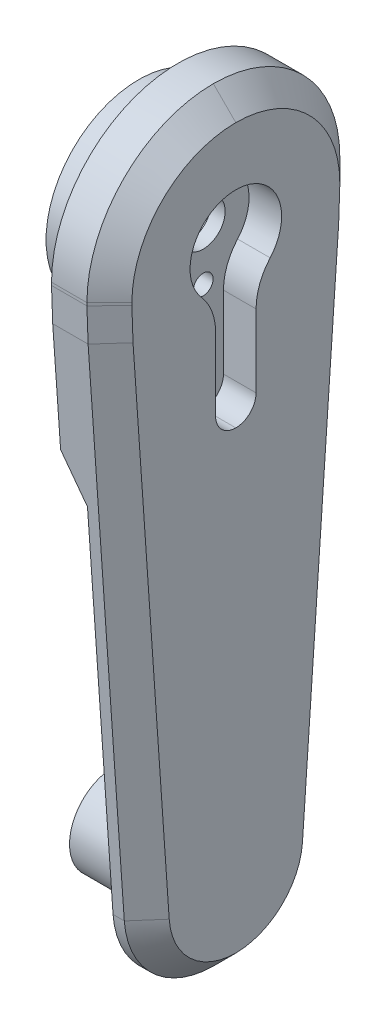
SolidWorks part; units mm, degrees
ref_plane "Front Plane" through (0, 0, 0) normal (0, 0, 1) x (1, 0, 0)
ref_plane "Top Plane" through (0, 0, 0) normal (0, 1, 0) x (1, 0, 0)
ref_plane "Right Plane" through (0, 0, 0) normal (1, 0, 0) x (0, 0, -1)
sketch "Sketch1" plane through (0, 0, 0) normal (1, 0, 0) x (0, 0, -1)
  line L1 (-10, 10) -> (10, 10)
  line L2 (-10, 10) -> (-10, -10)
  line L3 (-10, -10) -> (10, -10)
  line L4 (10, 10) -> (10, -10)
  line L5 (-10, 10) -> (10, -10) construction
  line L6 (-10, -10) -> (10, 10) construction
  point P0 (0, 0)
  dimension "D1" = 20
  dimension "D2" = 20
extrude "Boss-Extrude1" add sketch "Sketch1" along normal blind 20
sketch "Sketch2" plane through (20, 0, 0) normal (1, 0, 0) x (0, 0, -1)
  line L1 (-22.5, 35) -> (22.5, 35)
  line L2 (-22.5, 35) -> (-22.5, -35)
  line L3 (-22.5, -35) -> (22.5, -35)
  line L4 (22.5, 35) -> (22.5, -35)
  line L5 (-22.5, 35) -> (22.5, -35) construction
  line L6 (-22.5, -35) -> (22.5, 35) construction
  point P0 (0, 0)
  dimension "D1" = 45
  dimension "D2" = 70
extrude "Boss-Extrude2" add sketch "Sketch2" along normal blind 8.3
sketch "Sketch4" plane through (28.3, 0, 0) normal (1, 0, 0) x (0, 0, -1)
  line L0 (0, 7.65) -> (0, 8.1702) construction
  line L1 (7.65, 7.65) -> (-7.65, 7.65) construction
  line L17 (3.6, -26.55) -> (-3.6, -26.55) construction
  line L18 (-7.65, 7.65) -> (7.65, 7.65) construction
  line L22 (-7.65, 7.65) -> (-7.65, -27.55) construction
  line L23 (-7.65, -27.55) -> (7.65, -27.55) construction
  line L24 (7.65, 7.65) -> (7.65, -27.55) construction
  line L25 (-7.65, 7.65) -> (7.65, -27.55) construction
  line L26 (-7.65, -27.55) -> (7.65, 7.65) construction
  line L27 (3.6, -26.55) -> (3.6, -28.55) construction
  line L28 (3.6, -28.55) -> (-3.6, -28.55) construction
  line L29 (-3.6, -26.55) -> (-3.6, -28.55) construction
  line L30 (3.6, -26.55) -> (-3.6, -28.55) construction
  line L31 (3.6, -28.55) -> (-3.6, -26.55) construction
  line L34 (3.6, -28.55) -> (-3.6, -28.55)
  line L35 (-3.6, -28.55) -> (-3.6, -7.3118)
  line L36 (3.6, -28.55) -> (3.6, -7.3118)
  arc A1 (3.6, -6.75) -> (-3.6, -6.75) centre (0, 0) ccw construction
  arc A2 (3.6, -7.3118) -> (-3.6, -7.3118) centre (0, 0) ccw
  point P1 (0, -27.55)
  point P7 (0, -13.75)
  point P10 (0, 7.65)
  point P14 (0, -9.95)
  dimension "D1" = 15.3
  dimension "D5" = 2
  dimension "D2" = 15.3
  dimension "D3" = 35.2
  dimension "D4" = 7.2
extrude "Cut-Extrude1" cut sketch "Sketch4" against normal blind 5.8
fillet "Fillet1" radius 3.6 2 edges at (25.4, -28.55, 3.6) (25.4, -28.55, -3.6)
fillet "Fillet2" radius 10 2 edges at (25.4, -7.3118, 3.6) (25.4, -7.3118, -3.6)
sketch "Sketch5" plane through (0, 0, 0) normal (-1, 0, 0) x (0, 0, 1)
  circle A0 centre (0, 0) radius 3.9
  dimension "D1" = 7.8
extrude "Cut-Extrude2" cut sketch "Sketch5" against normal through all
sketch "Sketch6" plane through (22.5, 0, 0) normal (1, 0, 0) x (0, 0, -1)
  line L0 (0, -19.35) -> (0, 0) construction
  line L1 (0, -25.65) -> (0, -23.15) construction
  line L2 (0, -23.15) -> (0, -21.85) construction
  line L3 (0, -21.85) -> (0, -19.35) construction
  line L5 (0, 0) -> (1.164, 0) construction
  line L6 (0, 0) -> (0, -9.35) construction
  line L7 (0, -9.35) -> (1.164, -9.35) construction
  line L8 (1.164, 0) -> (1.164, -9.35) construction
  line L9 (0, 0) -> (1.164, -9.35) construction
  line L10 (0, -9.35) -> (1.164, 0) construction
  circle A0 centre (0, -20.6) radius 1.75
  circle A1 centre (0, -9.35) radius 1.75
  point P11 (0.582, -4.675)
  dimension "D5" = 3.5
  dimension "D6" = 9.35
  dimension "D7" = 3.5
  dimension "D1" = 19.35
  dimension "D2" = 2.5
  dimension "D3" = 1.3
  dimension "D4" = 2.5
extrude "Cut-Extrude3" cut sketch "Sketch6" against normal up to next
sketch "Sketch13" plane through (0, 0, 0) normal (-1, 0, 0) x (0, 0, 1)
  line L1 (-10, 10) -> (10, 10)
  line L2 (-10, 10) -> (-10, -10)
  line L3 (-10, -10) -> (10, -10)
  line L4 (10, 10) -> (10, -10)
extrude "Cut-Extrude9" cut sketch "Sketch13" against normal up to surface (20 mm away) up to face at (20, -20.6, -1.75)
sketch "Sketch14" plane through (20, 0, 0) normal (-1, 0, 0) x (0, 0, 1)
  line L0 (0, -11.1) -> (0, -18.85) construction
  circle A0 centre (0, -9.35) radius 1.75 construction
  circle A1 centre (0, -20.6) radius 1.75 construction
  circle A3 centre (0, 0) radius 16.475
  circle A4 centre (0, 0) radius 3.9 construction
  point P7 (0, -14.975)
  dimension "D1" = 32.95
  dimension "D2" = 12.575
extrude "Boss-Extrude3" add sketch "Sketch14" along normal blind 7.6 contours A3
sketch "Sketch15" plane through (0, 35, 0) normal (0, 1, 0) x (1, 0, 0)
  line L1 (20, 22.5) -> (28.3, 22.5)
  line L2 (20, 22.5) -> (20, -22.5)
  line L3 (20, -22.5) -> (28.3, -22.5)
  line L4 (28.3, 22.5) -> (28.3, -22.5)
extrude "Cut-Extrude10" cut sketch "Sketch15" against normal blind 12.5
sketch "Sketch16" plane through (12.4, 0, 0) normal (-1, 0, 0) x (0, 0, 1)
  circle A4 centre (0, 0) radius 13.475
  circle A5 centre (0, 0) radius 13.475
  dimension "D1" = 3
extrude "Cut-Extrude11" cut sketch "Sketch16" against normal blind 7.6
sketch "Sketch17" plane through (20, 0, 0) normal (-1, 0, 0) x (0, 0, 1)
  line L0 (0, 0) -> (-22.5, 0) construction
  line L1 (-22.5, -35) -> (-22.5, 22.5) construction
  line L2 (0, 0) -> (22.5, 0) construction
  line L3 (22.5, 22.5) -> (22.5, -35) construction
  line L4 (0, 0) -> (0, 22.5) construction
  line L5 (-22.5, 22.5) -> (22.5, 22.5) construction
sketch "Sketch18" plane through (0, -35, 0) normal (0, -1, 0) x (1, 0, 0)
  line L0 (20, 0) -> (20, 22.5) construction
  line L1 (20, 22.5) -> (28.3, 22.5)
  line L2 (20, 22.5) -> (20, -22.5)
  line L3 (20, -22.5) -> (28.3, -22.5)
  line L4 (28.3, 22.5) -> (28.3, -22.5)
  line L5 (28.3, 22.5) -> (20, 22.5) construction
  line L6 (28.3, 22.5) -> (28.3, -22.5) construction
extrude "Boss-Extrude4" add sketch "Sketch18" along normal blind 78.5
sketch "Sketch20" plane through (20, 0, 0) normal (-1, 0, 0) x (0, 0, 1)
  line L0 (0, 0) -> (0, -100) construction
  line L1 (22.5, 22.5) -> (22.5, -113.5) construction
  line L2 (-22.5, -113.5) -> (22.5, -113.5)
  line L3 (-22.5, -113.5) -> (-22.5, -33.5)
  line L4 (-22.5, -33.5) -> (22.5, -33.5)
  line L5 (22.5, -113.5) -> (22.5, -33.5)
  dimension "D1" = 100
  dimension "D2" = 80
fillet "Fillet5" radius 22.5 2 edges at (24.15, 22.5, -22.5) (24.15, 22.5, 22.5)
extrude "Cut-Extrude12" cut sketch "Sketch20" against normal blind 2.3
sketch "Sketch21" plane through (22.3, 0, 0) normal (-1, 0, 0) x (0, 0, 1)
  line L0 (0, -113.5) -> (0, -99.5) construction
  line L1 (-22.5, -113.5) -> (22.5, -113.5) construction
  circle A0 centre (0, -99.5) radius 8
  dimension "D2" = 16
  dimension "D1" = 14
extrude "Boss-Extrude5" add sketch "Sketch21" along normal blind 15.6
chamfer "Chamfer2" distance 110 angle 4 2 edges at (25.3, -113.5, -22.5) (25.3, -113.5, 22.5) first distance on face at (23.5333, -49, -22.5) first distance on face at (23.5333, -49, 22.5)
chamfer "Chamfer3" distance 3 angle 2 2 edges at (24.15, -3.5, 22.5) (24.15, -3.5, -22.5) first distance on face at (23.5333, -50.1667, 19.2367) first distance on face at (23.5333, -50.1667, -19.2367)
fillet "Fillet6" radius 16 2 edges at (25.3, -113.5, -14.8081) (25.3, -113.5, 14.8081)
chamfer "Chamfer4" distance 4 angle 45 10 edges at (28.3, -3.4963, -22.3954) (28.3, -0.25, -22.5) (28.3, 15.9099, -15.9099) (28.3, 15.9099, 15.9099) (28.3, -0.25, 22.5) (28.3, -3.4963, 22.3954) (28.3, -52.5544, 19.0698) (28.3, -109.1633, 10.8407) (28.3, -109.1633, -10.8407) (28.3, -52.5544, -19.0698)
sketch "Sketch23" plane through (6.7, 0, 0) normal (-1, 0, 0) x (0, 0, 1)
  line L0 (0, -99.5) -> (-8, -99.5) construction
  line L1 (0, -99.5) -> (8, -99.5) construction
  circle A0 centre (0, -99.5) radius 8 construction
  circle A1 centre (-4, -99.5) radius 2.35
  circle A2 centre (4, -99.5) radius 2.35
  point P0 (0, -99.5)
  dimension "D1" = 4.7
  dimension "D2" = 4.7
extrude "Cut-Extrude13" cut sketch "Sketch23" against normal blind 8 contours A2 | A1
chamfer "Chamfer5" distance 1 angle 45 2 edges at (6.7, -99.5, 6.35) (6.7, -99.5, -1.65)
sketch "Sketch24" plane through (20, 0, 0) normal (-1, 0, 0) x (0, 0, 1)
  line L0 (0, 0) -> (0, 13.475) construction
  line L1 (-16.475, 0) -> (-5.975, 0) construction
  line L3 (3.9, 0) -> (16.475, 0) construction
  circle A0 centre (0, 0) radius 3.9 construction
  circle A4 centre (0, 0) radius 16.475 construction
  circle A5 centre (-11.225, 0) radius 5
  circle A6 centre (0, 0) radius 13.475 construction
  circle A7 centre (11.225, 0) radius 5
  dimension "D1" = 10.5
  dimension "D2" = 10
extrude "Boss-Extrude6" add sketch "Sketch24" along normal up to surface (7.6 mm away) up to face at (12.4, 0, 13.475)
sketch "Sketch27" plane through (12.4, 0, 0) normal (-1, 0, 0) x (0, 0, 1)
  line L0 (-16.475, 0) -> (-5.975, 0) construction
  line L1 (0, 0) -> (-22.5, 0) construction
  line L2 (0, 0) -> (0, 5.9787) construction
  line L3 (0, 0) -> (0, 22.5) construction
  circle A0 centre (0, 0) radius 16.475 construction
  circle A1 centre (-11.225, 0) radius 2.35
  circle A2 centre (11.225, 0) radius 2.35
  dimension "D2" = 4.7
  dimension "D1" = 10.5
extrude "Cut-Extrude14" cut sketch "Sketch27" against normal blind 8 contours A1 | A2
sketch "Sketch28" plane through (20, 0, 0) normal (-1, 0, 0) x (0, 0, 1)
  line L7 (20.4022, -33.5) -> (22.2907, -6.4927)
  line L8 (22.2907, -6.4927) -> (22.5, -0.5)
  line L9 (22.5, -0.5) -> (22.5, 0)
  line L10 (-22.5, 0) -> (-22.5, -0.5)
  line L11 (-22.5, -0.5) -> (-22.2907, -6.4927)
  line L12 (-22.2907, -6.4927) -> (-20.4022, -33.5)
  line L13 (-20.4022, -33.5) -> (20.4022, -33.5)
  line L14 (20.4022, -33.5) -> (22.2907, -6.4927)
  line L15 (22.2907, -6.4927) -> (22.5, -0.5)
  line L16 (22.5, -0.5) -> (22.5, 0)
  line L17 (-22.5, 0) -> (-22.5, -0.5)
  line L18 (-22.5, -0.5) -> (-22.2907, -6.4927)
  line L19 (-22.2907, -6.4927) -> (-20.4022, -33.5)
  line L21 (-20.4022, -33.5) -> (20.4022, -33.5)
  circle A0 centre (0, 0) radius 16.475 construction
  circle A1 centre (0, -20.6) radius 1.75 construction
  arc A2 (22.5, 0) -> (0, 22.5) centre (0, 0) ccw
  arc A3 (0, 22.5) -> (-22.5, 0) centre (0, 0) ccw
  arc A4 (22.5, 0) -> (0, 22.5) centre (0, 0) ccw
  arc A5 (0, 22.5) -> (-22.5, 0) centre (0, 0) ccw
  circle A6 centre (0, 0) radius 16.475
  circle A7 centre (0, -20.6) radius 1.75
  dimension "D1" = 0
extrude "Boss-Extrude7" add sketch "Sketch28" along normal blind 2 contours L14 L15 L16 A4 A5 L17 L18 L19 L21 | A7 | A6
sketch "Sketch30" plane through (12.4, 0, 0) normal (-1, 0, 0) x (0, 0, 1)
  circle A1 centre (0, 0) radius 16.475
  circle A2 centre (0, 0) radius 16.475
  circle A3 centre (-11.225, 0) radius 2.35
  circle A4 centre (-11.225, 0) radius 2.35
  circle A5 centre (11.225, 0) radius 2.35
  arc A6 (12.5869, 4.8109) -> (-12.5869, 4.8109) centre (0, 0) ccw
  arc A7 (-12.5869, -4.8109) -> (-12.5869, 4.8109) centre (-11.225, 0) ccw
  arc A8 (-12.5869, -4.8109) -> (12.5869, -4.8109) centre (0, 0) ccw
  arc A9 (12.5869, 4.8109) -> (12.5869, -4.8109) centre (11.225, 0) ccw
  arc A10 (12.5869, 4.8109) -> (-12.5869, 4.8109) centre (0, 0) ccw
  arc A11 (-12.5869, -4.8109) -> (-12.5869, 4.8109) centre (-11.225, 0) ccw
  arc A12 (-12.5869, -4.8109) -> (12.5869, -4.8109) centre (0, 0) ccw
  arc A13 (12.5869, 4.8109) -> (12.5869, -4.8109) centre (11.225, 0) ccw
  circle A14 centre (11.225, 0) radius 2.35
  dimension "D1" = 0
  dimension "D2" = 0
  dimension "D3" = 0
  dimension "D4" = 0
extrude "Boss-Extrude8" add sketch "Sketch30" along normal blind 1.4
fillet "Fillet7" radius 2 4 edges at (15.5, -4.8109, 12.5869) (15.5, 4.8109, 12.5869) (15.5, 4.8109, -12.5869) (15.5, -4.8109, -12.5869)
fillet "Fillet8" radius 1.5 8 edges at (20, -6.076, -11.1856) (20, 0, -6.225) (20, 6.076, -11.1856) (20, 13.475, 0) (20, 6.076, 11.1856) (20, 0, 6.225) (20, -6.076, 11.1856) (20, -13.475, 0)
chamfer "Chamfer6" distance 1 angle 45 2 edges at (11, 0, -8.875) (11, 0, 13.575)
sketch "Sketch31" plane through (18, 0, 0) normal (-1, 0, 0) x (0, 0, 1)
  circle A0 centre (0, -20.6) radius 3.05
  dimension "D1" = 6.1
extrude "Cut-Extrude15" cut sketch "Sketch31" against normal blind 2.3
fillet "Fillet9" radius 1 1 edges at (18, -20.6, 3.05)
chamfer "Chamfer7" distance 4.3 angle 58 1 edges at (18, -33.5, 0) first distance on face at (20.15, -33.5, 0)
